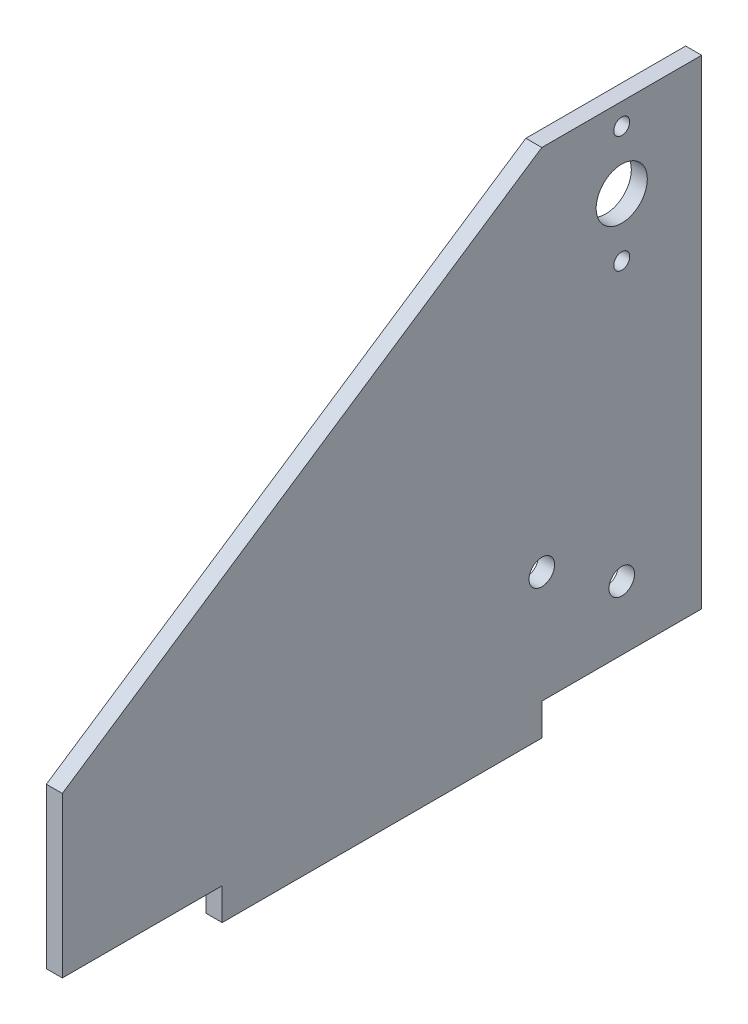
SolidWorks part; units mm, degrees
ref_plane "Alzado" through (0, 0, 0) normal (0, 0, 1) x (1, 0, 0)
ref_plane "Planta" through (0, 0, 0) normal (0, 1, 0) x (1, 0, 0)
ref_plane "Vista lateral" through (0, 0, 0) normal (1, 0, 0) x (0, 0, -1)
sketch "Croquis1" plane through (0, 0, 0) normal (1, 0, 0) x (0, 0, -1)
  line L0 (50, 75) -> (-100, -25)
  line L1 (-100, -75) -> (-50, -75)
  line L2 (-100, -75) -> (-100, -25)
  line L3 (50, 75) -> (100, 75)
  line L4 (100, -75) -> (100, 75)
  line L5 (100, 0) -> (-62.5, 0) construction
  line L6 (75, 75) -> (75, -75) construction
  line L7 (0, 41.6667) -> (0, -85) construction
  line L9 (-50, -75) -> (-50, -85)
  line L10 (-50, -85) -> (50, -85)
  line L11 (50, -75) -> (50, -85)
  line L14 (50, -75) -> (100, -75)
  circle A0 centre (75, 50) radius 8
  circle A1 centre (75, -55) radius 4
  circle A2 centre (50, -40) radius 4
  circle A3 centre (75, 68.25) radius 2.5
  circle A4 centre (75, 31.75) radius 2.5
  point P0 (0, 0)
  point P13 (0, -75)
  dimension "D6" = 16
  dimension "D10" = 8
  dimension "D12" = 8
  dimension "D15" = 5
  dimension "D16" = 5
  dimension "D1" = 150
  dimension "D2" = 200
  dimension "D3" = 50
  dimension "D4" = 50
  dimension "D5" = 50
  dimension "D7" = 100
  dimension "D8" = 50
  dimension "D9" = 10
  dimension "D11" = 20
  dimension "D13" = 25
  dimension "D14" = 15
  dimension "D17" = 18.25
  dimension "D18" = 18.25
extrude "Saliente-Extruir1" add sketch "Croquis1" along normal blind 5
